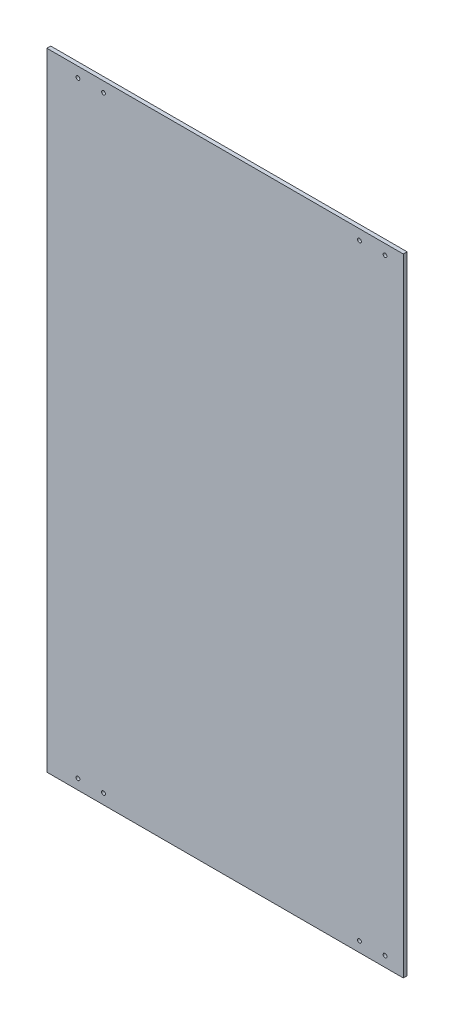
SolidWorks part; units mm, degrees
ref_plane "前视基准面" through (0, 0, 0) normal (0, 0, 1) x (1, 0, 0)
ref_plane "上视基准面" through (0, 0, 0) normal (0, 1, 0) x (1, 0, 0)
ref_plane "右视基准面" through (0, 0, 0) normal (1, 0, 0) x (0, 0, -1)
other "Configuration Table"
sketch "草图1" plane through (0, 0, 0) normal (0, 0, 1) x (1, 0, 0)
  line L1 (-139.28, 245) -> (139.28, 245)
  line L2 (-139.28, 245) -> (-139.28, -245)
  line L3 (-139.28, -245) -> (139.28, -245)
  line L4 (139.28, 245) -> (139.28, -245)
  line L5 (-139.28, 245) -> (139.28, -245) construction
  line L6 (-139.28, -245) -> (139.28, 245) construction
  circle A0 centre (104.9991, 237) radius 1.5
  circle A1 centre (124.9991, 237) radius 1.5
  circle A2 centre (-95.0009, 237) radius 1.5
  circle A3 centre (-115.0009, 237) radius 1.5
  circle A4 centre (124.9991, -237) radius 1.5
  circle A5 centre (104.9991, -237) radius 1.5
  circle A6 centre (-95.0009, -237) radius 1.5
  circle A7 centre (-115.0009, -237) radius 1.5
  point P0 (0, 0)
  dimension "D1" = 490
  dimension "D2" = 278.56
extrude "凸台-拉伸1" add sketch "草图1" along normal blind 3
